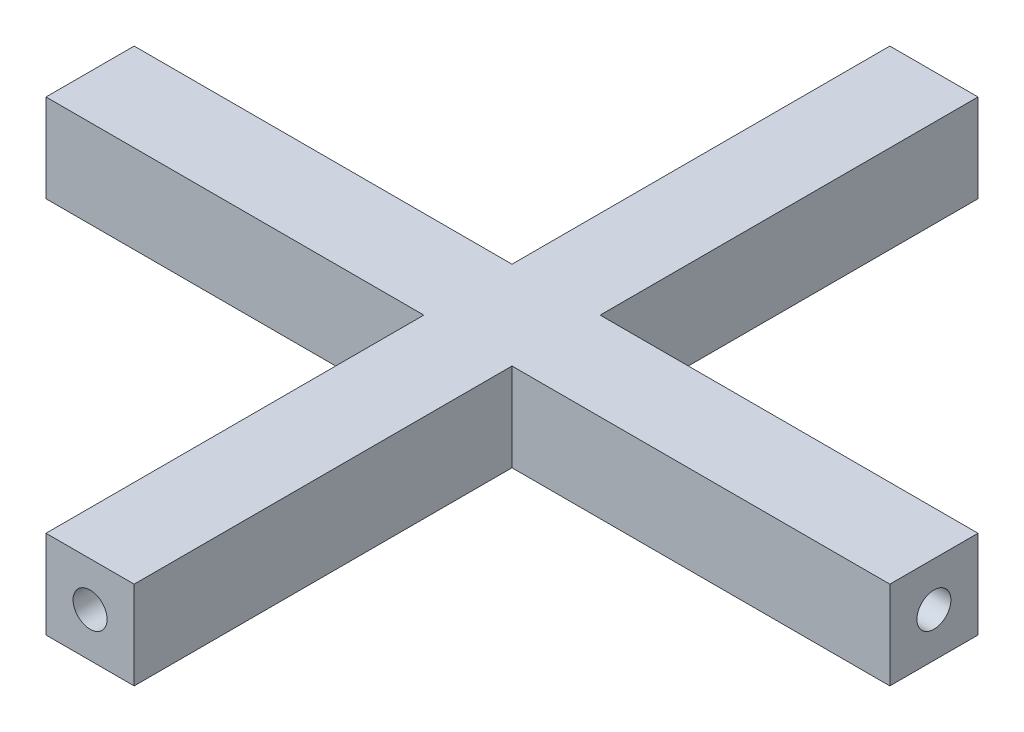
SolidWorks part; units mm, degrees
ref_plane "Front Plane" through (0, 0, 0) normal (0, 0, 1) x (1, 0, 0)
ref_plane "Top Plane" through (0, 0, 0) normal (0, 1, 0) x (1, 0, 0)
ref_plane "Right Plane" through (0, 0, 0) normal (1, 0, 0) x (0, 0, -1)
sketch "Sketch1" plane through (0, 0, 0) normal (0, 1, 0) x (1, 0, 0)
  line L24 (1.75, -1.75) -> (1.75, -16.75)
  line L25 (-1.75, 16.75) -> (1.75, 16.75)
  line L26 (-1.75, 16.75) -> (-1.75, 1.75)
  line L27 (-1.75, -16.75) -> (1.75, -16.75)
  line L28 (1.75, 16.75) -> (1.75, 1.75)
  line L31 (-16.75, 1.75) -> (-1.75, 1.75)
  line L32 (-16.75, 1.75) -> (-16.75, -1.75)
  line L33 (-16.75, -1.75) -> (-1.75, -1.75)
  line L34 (16.75, 1.75) -> (16.75, -1.75)
  line L39 (-1.75, -1.75) -> (-1.75, -16.75)
  line L41 (1.75, 1.75) -> (16.75, 1.75)
  line L43 (1.75, -1.75) -> (16.75, -1.75)
  point P0 (0, 0)
  point P5 (0, 0)
  point P10 (0, 0)
  point P12 (0, 16.75)
  point P13 (0, 0)
  point P16 (-16.75, 0)
  dimension "D1" = 3.5
  dimension "D2" = 15
extrude "Boss-Extrude1" add sketch "Sketch1" along normal mid plane 3.5
sketch "Sketch2" plane through (0, 0, 0) normal (0, 0, 1) x (1, 0, 0)
  circle A0 centre (0, 0) radius 0.675
  dimension "D1" = 1.35
extrude "Cut-Extrude4" cut sketch "Sketch2" against normal through all from surface starting at face at (-9.25, 0, -1.75)
extrude "Cut-Extrude5" cut sketch "Sketch2<2>" along normal through all from surface starting at face at (-9.25, 0, 1.75)
sketch "Sketch2<2>" plane through (0, 0, 0) normal (0, 0, 1) x (1, 0, 0) same geometry as "Sketch2"
sketch "Sketch3" plane through (0, 0, 0) normal (-1, 0, 0) x (0, 0, 1)
  circle A0 centre (0, 0) radius 0.675
  dimension "D1" = 1.35
extrude "Cut-Extrude6" cut sketch "Sketch3" along normal through all from surface starting at face at (-1.75, 0, -9.25)
extrude "Cut-Extrude7" cut sketch "Sketch3<2>" against normal through all from surface starting at face at (1.75, 0, -9.25)
sketch "Sketch3<2>" plane through (0, 0, 0) normal (-1, 0, 0) x (0, 0, 1) same geometry as "Sketch3"
